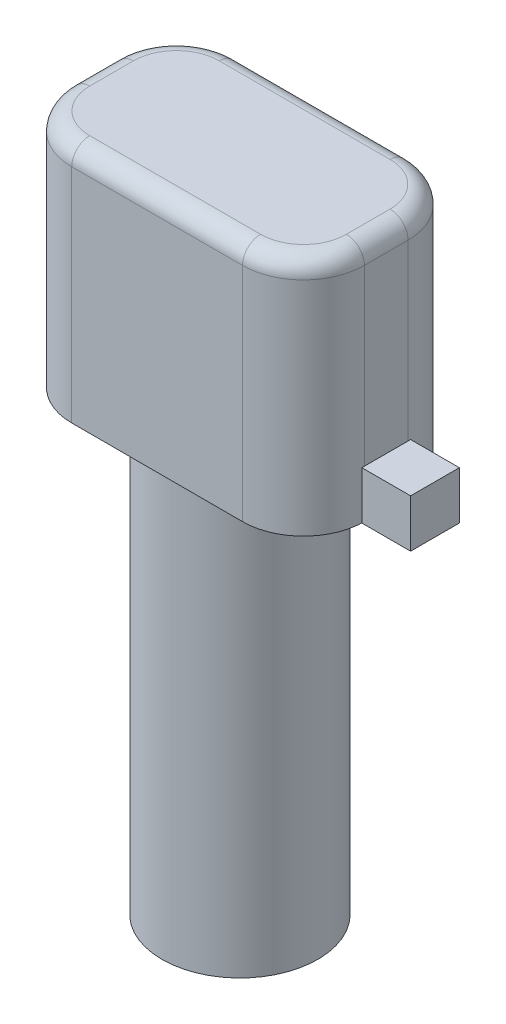
SolidWorks part; units mm, degrees
ref_plane "Front Plane" through (0, 0, 0) normal (0, 0, 1) x (1, 0, 0)
ref_plane "Top Plane" through (0, 0, 0) normal (0, 1, 0) x (1, 0, 0)
ref_plane "Right Plane" through (0, 0, 0) normal (1, 0, 0) x (0, 0, -1)
sketch "Sketch1" plane through (0, 0, 0) normal (0, 1, 0) x (1, 0, 0)
  circle A0 centre (0, 0) radius 3.25
  dimension "D1" = 6.5
extrude "Boss-Extrude1" add sketch "Sketch1" along normal blind 17.686 contours A0
sketch "Sketch2" plane through (0, 0, 0) normal (0, -1, 0) x (1, 0, 0)
  circle A1 centre (0, 0) radius 1.75
  dimension "D1" = 3.5
extrude "Cut-Extrude1" [suppressed] cut sketch "Sketch2" against normal blind 2.5
sketch "Sketch3" plane through (0, 17.686, 0) normal (0, 1, 0) x (1, 0, 0)
  line L1 (-6.1, 3.45) -> (6.1, 3.45)
  line L2 (-6.1, 3.45) -> (-6.1, -3.45)
  line L3 (-6.1, -3.45) -> (6.1, -3.45)
  line L4 (6.1, 3.45) -> (6.1, -3.45)
  line L5 (-6.1, 3.45) -> (6.1, -3.45) construction
  line L6 (-6.1, -3.45) -> (6.1, 3.45) construction
  point P0 (0, 0)
  dimension "D1" = 12.2
  dimension "D2" = 6.9
extrude "Boss-Extrude2" add sketch "Sketch3" along normal blind 10
fillet "Fillet1" radius 2.54 4 edges at (-6.1, 22.686, -3.45) (6.1, 22.686, -3.45) (6.1, 22.686, 3.45) (-6.1, 22.686, 3.45)
fillet "Fillet2" radius 0.75 8 edges at (6.1, 27.686, 0) (5.3561, 27.686, 2.7061) (5.3561, 27.686, -2.7061) (0, 27.686, -3.45) (-5.3561, 27.686, -2.7061) (-6.1, 27.686, 0) (-5.3561, 27.686, 2.7061) (0, 27.686, 3.45)
sketch "Sketch5" plane through (0, 17.686, 0) normal (0, -1, 0) x (1, 0, 0)
  line L0 (-6.1, 0) -> (6.1, 0) construction
  line L1 (-6.1, -0.91) -> (-6.1, 0.91) construction
  line L2 (6.1, 0.91) -> (6.1, -0.91) construction
  line L3 (6.1, 1.016) -> (8.132, 1.016)
  line L4 (8.132, 1.016) -> (8.132, -1.016)
  line L5 (8.132, -1.016) -> (6.1, -1.016)
  line L6 (8.132, 0) -> (6.1, 0) construction
  line L7 (6.1, 1.016) -> (6.1, -1.016)
  dimension "D1" = 2.032
  dimension "D2" = 2.032
extrude "Boss-Extrude3" add sketch "Sketch5" against normal blind 2
